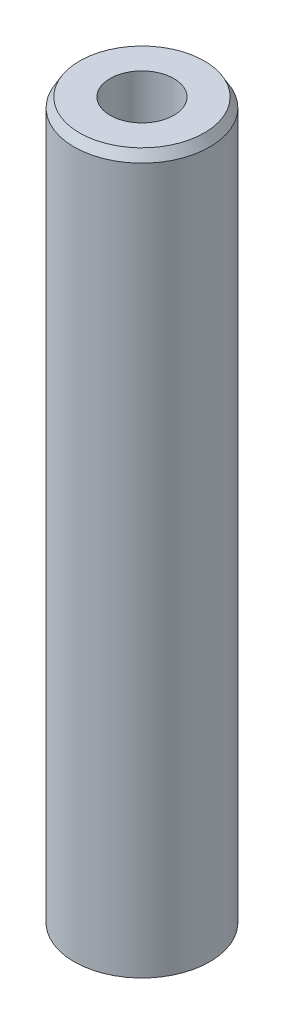
SolidWorks part; units mm, degrees
ref_plane "Front Plane" through (0, 0, 0) normal (0, 0, 1) x (1, 0, 0)
ref_plane "Top Plane" through (0, 0, 0) normal (0, 1, 0) x (1, 0, 0)
ref_plane "Right Plane" through (0, 0, 0) normal (1, 0, 0) x (0, 0, -1)
sketch "Sketch1" plane through (0, 0, 0) normal (0, 1, 0) x (1, 0, 0)
  circle A0 centre (0, 0) radius 20
  dimension "SHAFT_OD" = 40
extrude "Boss-Extrude1" add sketch "Sketch1" along normal blind 212.4577
sketch "Sketch2" plane through (0, 0, 0) normal (0, 1, 0) x (1, 0, 0)
  circle A0 centre (0, 0) radius 9.4036
  dimension "BORE_D" = 18.8072
extrude "Cut-Extrude1" cut sketch "Sketch2" along normal through all
chamfer "Chamfer1" distance 2.7876 angle 30 2 edges at (0, 212.4577, 20) (0, 0, 20) first distance on face at (0, 212.4577, 20) first distance on face at (0, 0, 9.4036)
